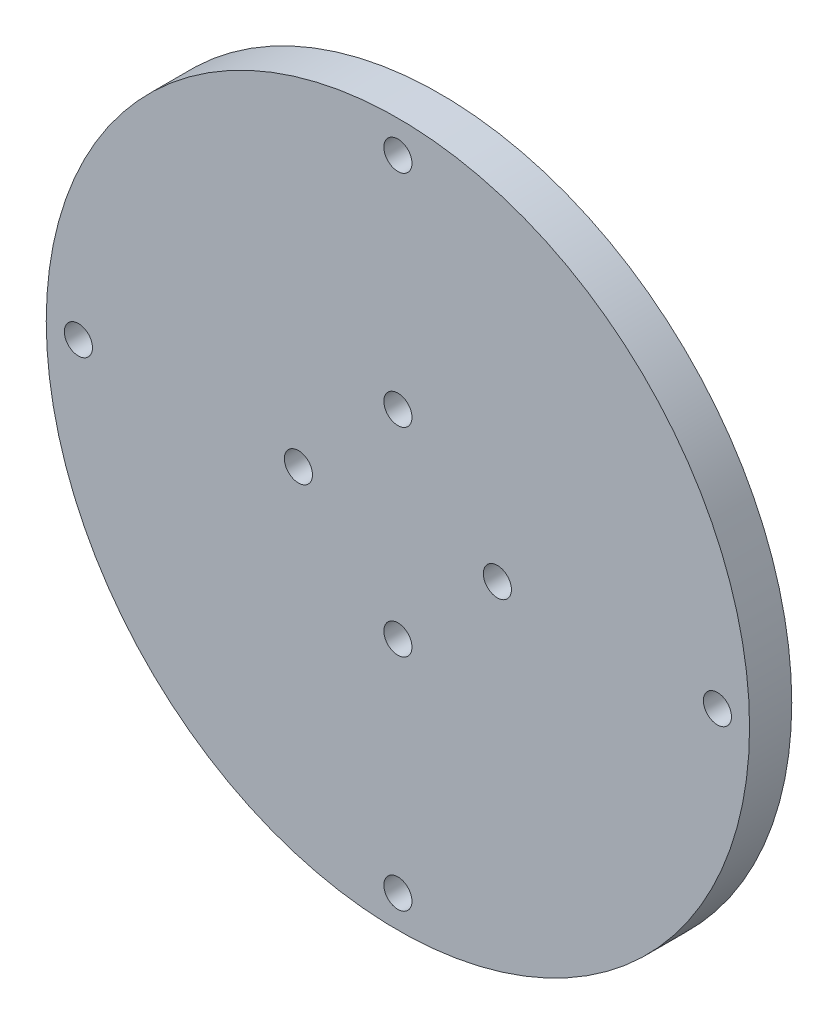
SolidWorks part; units mm, degrees
ref_plane "Front Plane" through (0, 0, 0) normal (0, 0, 1) x (1, 0, 0)
ref_plane "Top Plane" through (0, 0, 0) normal (0, 1, 0) x (1, 0, 0)
ref_plane "Right Plane" through (0, 0, 0) normal (1, 0, 0) x (0, 0, -1)
sketch "Sketch1" plane through (0, 0, 0) normal (0, 0, 1) x (1, 0, 0)
  line L0 (-25, 0) -> (25, 0) construction
  line L5 (0, 25) -> (0, -25) construction
  line L6 (-7.0711, 0) -> (0, 7.0711) construction
  line L7 (0, 7.0711) -> (7.0711, 0) construction
  line L8 (7.0711, 0) -> (0, -7.0711) construction
  line L9 (0, -7.0711) -> (-7.0711, 0) construction
  circle A0 centre (0, 0) radius 25
  circle A1 centre (0, 22.714) radius 1
  circle A2 centre (22.714, 0) radius 1
  circle A3 centre (0, -22.714) radius 1
  circle A4 centre (-22.714, 0) radius 1
  circle A11 centre (0, 7.0711) radius 1
  circle A12 centre (7.0711, 0) radius 1
  circle A13 centre (0, -7.0711) radius 1
  circle A14 centre (-7.0711, 0) radius 1
  point P5 (0, 25)
  point P16 (0, -25)
  dimension "D1" = 50
  dimension "D2" = 2
  dimension "D8" = 10
  dimension "D9" = 2
  dimension "D10" = 2
  dimension "D11" = 2
  dimension "D12" = 2
  dimension "D3" = 2.286
  dimension "D5" = 2.286
  dimension "D6" = 90
  dimension "D7" = 90
  dimension "D4" = 4
extrude "Boss-Extrude1" add sketch "Sketch1" along normal mid plane 3 contours A0 A12 A13 A4 A3 A2 A1 | A13 A12 region at (0, 0, 0)
